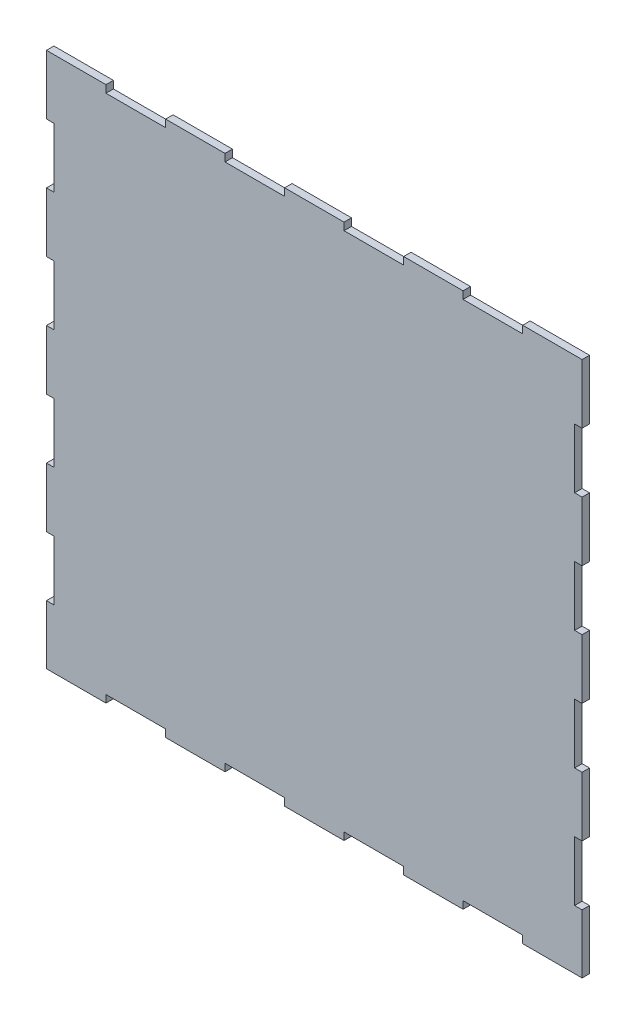
SolidWorks part; units mm, degrees
ref_plane "Front Plane" through (0, 0, 0) normal (0, 0, 1) x (1, 0, 0)
ref_plane "Top Plane" through (0, 0, 0) normal (0, 1, 0) x (1, 0, 0)
ref_plane "Right Plane" through (0, 0, 0) normal (1, 0, 0) x (0, 0, -1)
sketch "Sketch2" plane through (0, 0, 0) normal (0, 0, 1) x (1, 0, 0)
  line L0 (-57.15, -57.15) -> (57.15, 57.15) construction
  line L1 (-57.15, -57.15) -> (57.15, -57.15)
  line L2 (-57.15, -57.15) -> (-57.15, 57.15)
  line L3 (-57.15, 57.15) -> (57.15, 57.15)
  line L4 (57.15, -57.15) -> (57.15, 57.15)
  line L5 (57.15, -57.15) -> (-57.15, 57.15) construction
  point P0 (11.6615, 11.6615)
  point P5 (0, 0)
  dimension "D2" = 114.3
  dimension "D3" = 114.3
extrude "Boss-Extrude1" add sketch "Sketch2" along normal blind 1.5875
sketch "Sketch3" plane through (0, 0, 1.5875) normal (0, 0, 1) x (1, 0, 0)
  line L20 (-57.15, 57.15) -> (-57.15, 44.45) construction
  line L21 (-57.15, -57.15) -> (57.15, -57.15) construction
  line L22 (-57.15, 19.0246) -> (-57.15, 6.2992)
  line L23 (-57.15, 44.45) -> (-55.56, 44.45)
  line L24 (-57.15, 44.45) -> (-57.15, 31.7246)
  line L25 (-57.15, 31.7246) -> (-55.56, 31.7246)
  line L26 (-55.56, 44.45) -> (-55.56, 31.7246)
  line L27 (-57.15, 19.0246) -> (-55.56, 19.0246)
  line L28 (-55.56, 19.0246) -> (-55.56, 6.2992)
  line L29 (-57.15, 6.2992) -> (-55.56, 6.2992)
  line L30 (-57.15, -6.4008) -> (-57.15, -19.1262)
  line L31 (-57.15, -6.4008) -> (-55.56, -6.4008)
  line L32 (-55.56, -6.4008) -> (-55.56, -19.1262)
  line L33 (-57.15, -19.1262) -> (-55.56, -19.1262)
  line L34 (-57.15, -31.8262) -> (-57.15, -44.5516)
  line L35 (-57.15, -31.8262) -> (-55.56, -31.8262)
  line L36 (-55.56, -31.8262) -> (-55.56, -44.5516)
  line L37 (-57.15, -44.5516) -> (-55.56, -44.5516)
  line L38 (-57.15, 57.15) -> (-44.45, 57.15) construction
  line L39 (-55.56, 31.7246) -> (-55.56, 19.0246) construction
  line L60 (-57.15, 57.15) -> (-57.15, -57.15) construction
  line L61 (57.15, 57.15) -> (57.15, 44.45) construction
  line L62 (57.15, 57.15) -> (-57.15, 57.15) construction
  line L63 (57.15, 19.0246) -> (57.15, 6.2992)
  line L64 (57.15, 44.45) -> (55.56, 44.45)
  line L65 (57.15, 44.45) -> (57.15, 31.7246)
  line L66 (57.15, 31.7246) -> (55.56, 31.7246)
  line L67 (55.56, 44.45) -> (55.56, 31.7246)
  line L68 (57.15, 19.0246) -> (55.56, 19.0246)
  line L69 (55.56, 19.0246) -> (55.56, 6.2992)
  line L70 (57.15, 6.2992) -> (55.56, 6.2992)
  line L71 (57.15, -6.4008) -> (57.15, -19.1262)
  line L72 (57.15, -6.4008) -> (55.56, -6.4008)
  line L73 (55.56, -6.4008) -> (55.56, -19.1262)
  line L74 (57.15, -19.1262) -> (55.56, -19.1262)
  line L75 (57.15, -31.8262) -> (57.15, -44.5516)
  line L76 (57.15, -31.8262) -> (55.56, -31.8262)
  line L77 (55.56, -31.8262) -> (55.56, -44.5516)
  line L78 (57.15, -44.5516) -> (55.56, -44.5516)
  line L79 (55.56, 31.7246) -> (55.56, 19.0246) construction
  line L80 (-19.05, 57.15) -> (-19.05, 55.56)
  line L81 (-44.45, 57.15) -> (-31.7246, 57.15)
  line L82 (-44.45, 57.15) -> (-44.45, 55.56)
  line L83 (-44.45, 55.56) -> (-31.7246, 55.56)
  line L84 (-31.7246, 57.15) -> (-31.7246, 55.56)
  line L85 (-19.05, 57.15) -> (-6.3246, 57.15)
  line L86 (-6.3246, 57.15) -> (-6.3246, 55.56)
  line L87 (-19.05, 55.56) -> (-6.3246, 55.56)
  line L88 (6.35, 57.15) -> (6.35, 55.56)
  line L89 (6.35, 57.15) -> (19.0754, 57.15)
  line L90 (19.0754, 57.15) -> (19.0754, 55.56)
  line L91 (6.35, 55.56) -> (19.0754, 55.56)
  line L92 (31.75, 57.15) -> (31.75, 55.56)
  line L93 (31.75, 57.15) -> (44.4754, 57.15)
  line L94 (44.4754, 57.15) -> (44.4754, 55.56)
  line L95 (31.75, 55.56) -> (44.4754, 55.56)
  line L96 (-31.7246, 57.15) -> (-19.05, 57.15) construction
  line L97 (-57.15, -57.15) -> (-44.45, -57.15) construction
  line L99 (-19.05, -57.15) -> (-19.05, -55.56)
  line L100 (-44.45, -57.15) -> (-31.7246, -57.15)
  line L101 (-44.45, -57.15) -> (-44.45, -55.56)
  line L102 (-44.45, -55.56) -> (-31.7246, -55.56)
  line L103 (-31.7246, -57.15) -> (-31.7246, -55.56)
  line L104 (-19.05, -57.15) -> (-6.3246, -57.15)
  line L105 (-6.3246, -57.15) -> (-6.3246, -55.56)
  line L106 (-19.05, -55.56) -> (-6.3246, -55.56)
  line L107 (6.35, -57.15) -> (6.35, -55.56)
  line L108 (6.35, -57.15) -> (19.0754, -57.15)
  line L109 (19.0754, -57.15) -> (19.0754, -55.56)
  line L110 (6.35, -55.56) -> (19.0754, -55.56)
  line L111 (31.75, -57.15) -> (31.75, -55.56)
  line L112 (31.75, -57.15) -> (44.4754, -57.15)
  line L113 (44.4754, -57.15) -> (44.4754, -55.56)
  line L114 (31.75, -55.56) -> (44.4754, -55.56)
  line L115 (-31.7246, -55.56) -> (-19.05, -55.56) construction
  dimension "D2" = 12.7
  dimension "D4" = 12.7
  dimension "D5" = 12.7254
  dimension "D6" = 1.59
  dimension "D8" = 12.7254
  dimension "D9" = 12.7
  dimension "D10" = 4
  dimension "D11" = 12.6746
  dimension "D13" = 12.7
  dimension "D14" = 1.59
  dimension "D15" = 12.7254
  dimension "D16" = 1.59
  dimension "D18" = 12.7
  dimension "D3" = 1.59
  dimension "D12" = 12.7
  dimension "D19" = 12.7254
  dimension "D21" = 12.6746
  dimension "D7" = 4
  dimension "D17" = 4
  dimension "D20" = 4
extrude "Cut-Extrude1" cut sketch "Sketch3" against normal through all
